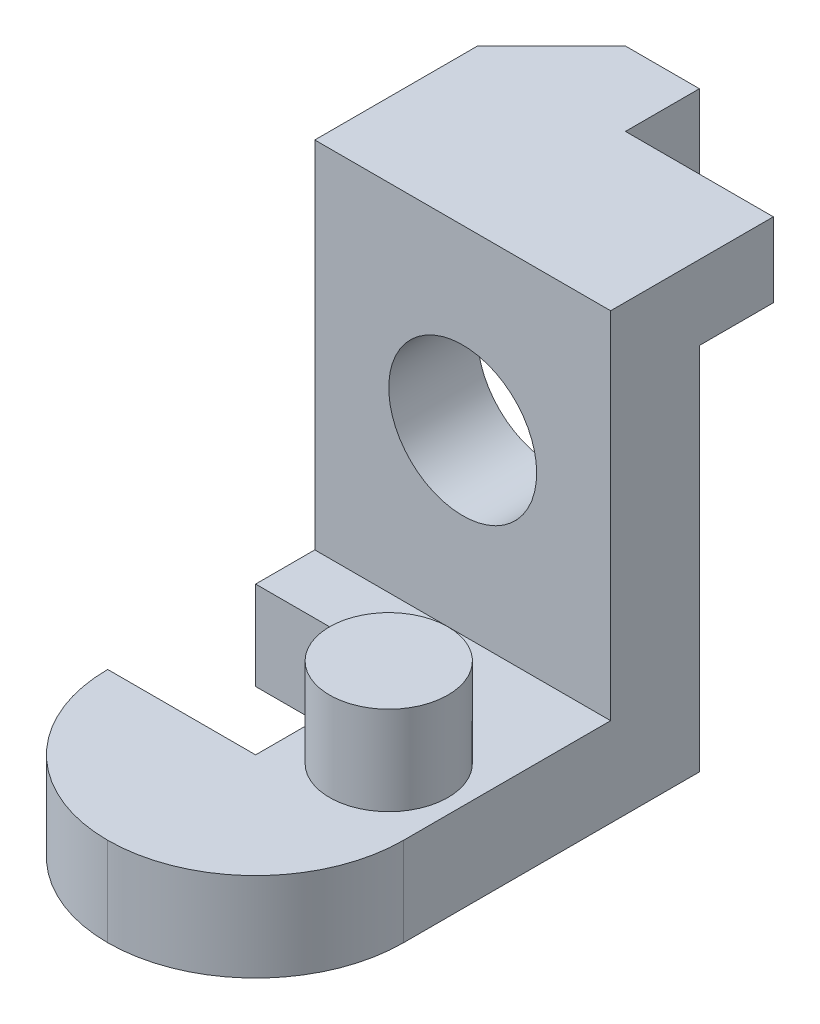
SolidWorks part; units mm, degrees
ref_plane "Front Plane" through (0, 0, 0) normal (0, 0, 1) x (1, 0, 0)
ref_plane "Top Plane" through (0, 0, 0) normal (0, 1, 0) x (1, 0, 0)
ref_plane "Right Plane" through (0, 0, 0) normal (1, 0, 0) x (0, 0, -1)
sketch "Sketch1" plane through (0, 0, 0) normal (0, 1, 0) x (1, 0, 0)
  line L0 (0, 0) -> (0, 50.8)
  line L1 (0, 50.8) -> (25.4, 50.8)
  line L2 (25.4, 50.8) -> (25.4, 0)
  line L3 (25.4, 0) -> (0, 0)
  dimension "D1" = 50.8
  dimension "D2" = 25.4
  dimension "D3" = 50.8
extrude "Boss-Extrude1" add sketch "Sketch1" along normal blind 38.1 contours L0 L1 L2 L3
sketch "Sketch2" plane through (0, 38.1, 0) normal (0, 1, 0) x (1, 0, 0)
  line L0 (0, 0) -> (0, 30.48)
  line L1 (0, 0) -> (0, 50.8) construction
  line L2 (0, 30.48) -> (25.4, 30.48)
  line L3 (25.4, 50.8) -> (25.4, 0) construction
  line L4 (25.4, 30.48) -> (25.4, 0)
  line L5 (25.4, 0) -> (0, 0)
  dimension "D1" = 30.48
  dimension "D2" = 30.48
  dimension "D3" = 25.4
extrude "Cut-Extrude1" cut sketch "Sketch2" against normal blind 30.48
sketch "Sketch3" plane through (0, 0, 0) normal (-1, 0, 0) x (0, 0, 1)
  line L0 (-50.8, 0) -> (-50.8, 31.7068)
  line L1 (-50.8, 38.1) -> (-50.8, 0) construction
  line L2 (-50.8, 31.7068) -> (-38.1, 31.7068)
  line L3 (-38.1, 31.7068) -> (-38.1, 0)
  line L4 (0, 0) -> (-50.8, 0) construction
  line L5 (-38.1, 0) -> (-50.8, 0)
  line M6 (-50.8, 38.1) -> (-50.8, 0)
  line M7 (-50.8, 0) -> (0, 0)
  dimension "D1" = 12.7
  dimension "D2" = 12.7
  dimension "D3" = 31.7068
extrude "Cut-Extrude2" cut sketch "Sketch3" against normal blind 32.258 and the other way blind 10.668 contours L3 L2 M6 M7 region at (0, 15.8534, -44.45)
sketch "Sketch4" plane through (0, 38.1, 0) normal (0, 1, 0) x (1, 0, 0)
  line L0 (25.4, 50.8) -> (12.7, 50.8)
  line L1 (0, 50.8) -> (25.4, 50.8) construction
  line L2 (12.7, 50.8) -> (12.7, 44.45)
  line L3 (12.7, 44.45) -> (25.4, 44.45)
  line L4 (25.4, 50.8) -> (25.4, 30.48) construction
  line L5 (25.4, 44.45) -> (25.4, 50.8)
  dimension "D1" = 12.7
  dimension "D2" = 6.35
  dimension "D3" = 6.35
extrude "Cut-Extrude3" cut sketch "Sketch4" against normal blind 32.258
chamfer "Chamfer1" distance 6.35 angle 45 1 edges at (0, 34.9034, -50.8)
fillet "Fillet1" radius 12.7 1 edges at (25.4, 3.81, 0) type face fillet first side face at (12.7, 3.81, 0) second side face at (25.4, 19.3567, -28.2575)
fillet "Fillet2" radius 12.7 1 edges at (0, 3.81, 0) type face fillet first side face at (0, 19.3567, -28.2575) second side face at (6.35, 3.81, 0) tangent propagation no
sketch "Sketch8" plane through (0, 7.62, 0) normal (0, 1, 0) x (1, 0, 0)
  line L0 (25.4, 30.48) -> (19.05, 30.48)
  line L1 (25.4, 30.48) -> (0, 30.48) construction
  line L2 (19.05, 30.48) -> (19.05, 17.78)
  circle A0 centre (19.05, 17.78) radius 5.08
  dimension "D1" = 6.35
  dimension "D2" = 12.7
extrude "Boss-Extrude3" add sketch "Sketch8" along normal blind 7.62 contours A0 region at (15.5595, 7.62, -14.2895)
sketch "Sketch9" plane through (0, 0, -30.48) normal (0, 0, 1) x (1, 0, 0)
  circle A0 centre (12.7, 22.86) radius 6.35
extrude "Cut-Extrude6" cut sketch "Sketch9" against normal blind 7.62
sketch "Sketch10" plane through (0, 7.62, 0) normal (0, 1, 0) x (1, 0, 0)
  line L0 (0, 12.7) -> (12.7, 12.7)
  line L1 (12.7, 12.7) -> (12.7, 25.4)
  line L2 (12.7, 25.4) -> (0, 25.4)
  line L3 (0, 30.48) -> (0, 12.7) construction
  line L4 (0, 25.4) -> (0, 12.7)
  dimension "D1" = 12.7
  dimension "D2" = 12.7
extrude "Cut-Extrude7" cut sketch "Sketch10" against normal blind 7.62
